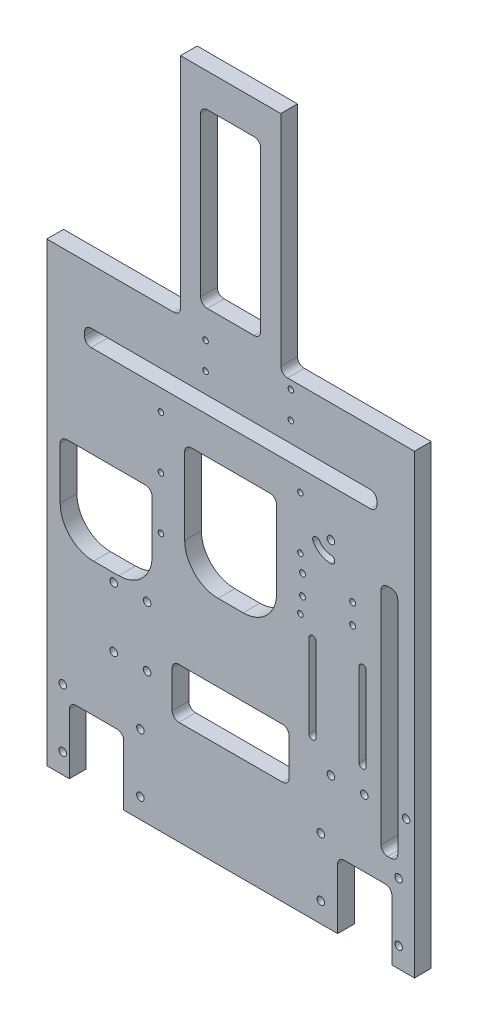
SolidWorks part; units mm, degrees
ref_plane "Front" through (0, 0, 0) normal (0, 0, 1) x (1, 0, 0)
ref_plane "Top" through (0, 0, 0) normal (0, 1, 0) x (1, 0, 0)
ref_plane "Right" through (0, 0, 0) normal (1, 0, 0) x (0, 0, -1)
sketch "Esquisse1" plane through (0, 0, 0) normal (0, 0, 1) x (1, 0, 0)
  line L1 (0, 0) -> (220, 0)
  line L2 (0, 0) -> (0, 285)
  line L3 (0, 285) -> (220, 285)
  line L4 (220, 0) -> (220, 285)
  dimension "D1" = 220
  dimension "D2" = 285
extrude "Boss.-Extru.1" add sketch "Esquisse1" along normal blind 10
sketch "Esquisse2" plane through (0, 0, 0) normal (0, -1, 0) x (1, 0, 0)
  line L0 (0, 5) -> (220, 5) construction
  line L1 (0, 10) -> (0, 0) construction
  line L2 (220, 10) -> (220, 0) construction
  line L3 (110, 5) -> (110, 28.0559) construction
  circle A0 centre (110, 5) radius 2
  circle A1 centre (213, 5) radius 2
  circle A2 centre (7, 5) radius 2
  dimension "D1" = 4
  dimension "D2" = 103
extrude "Enlèv. mat.-Extru.1" cut sketch "Esquisse2" against normal blind 8
sketch "Esquisse3" plane through (0, 0, 10) normal (0, 0, 1) x (1, 0, 0)
  line L0 (110, 0) -> (110, 285) construction
  line L1 (0, 0) -> (220, 0) construction
  line L2 (220, 285) -> (0, 285) construction
  line L3 (82.5, 208) -> (137.5, 208)
  line L4 (137.5, 208) -> (137.5, 138)
  line L5 (137.5, 138) -> (82.5, 138)
  line L6 (82.5, 208) -> (82.5, 138)
  line L8 (8, 175) -> (63, 175)
  line L9 (8, 175) -> (8, 120)
  line L10 (8, 120) -> (63, 120)
  line L11 (63, 175) -> (63, 120)
  line L12 (200, 55) -> (210, 55)
  line L13 (200, 55) -> (200, 195)
  line L14 (200, 195) -> (210, 195)
  line L15 (210, 55) -> (210, 195)
  point P11 (110, 138)
  point P12 (110, 208)
  dimension "D1" = 70
  dimension "D2" = 55
  dimension "D3" = 138
  dimension "D4" = 55
  dimension "D5" = 47
  dimension "D6" = 55
  dimension "D7" = 120
  dimension "D8" = 140
  dimension "D9" = 55
  dimension "D10" = 90
  dimension "D11" = 10
extrude "Enlèv. mat.-Extru.2" cut sketch "Esquisse3" against normal through all both and the other way through all
sketch "Esquisse5" plane through (0, 0, 10) normal (0, 0, 1) x (1, 0, 0)
  line L0 (110, 230) -> (110, 0) construction
  line L1 (22.5, 240) -> (197.5, 240)
  line L2 (22.5, 240) -> (22.5, 230)
  line L3 (22.5, 230) -> (197.5, 230)
  line L4 (197.5, 240) -> (197.5, 230)
  line L5 (0, 0) -> (220, 0) construction
  dimension "D1" = 175
  dimension "D2" = 10
  dimension "D3" = 230
extrude "Enlèv. mat.-Extru.3" cut sketch "Esquisse5" against normal through all both and the other way through all
sketch "Esquisse6" plane through (0, 0, 10) normal (0, 0, 1) x (1, 0, 0)
  line L0 (170, 80) -> (190, 80) construction
  line L1 (0, 0) -> (220, 0) construction
  line L2 (137.5, 138) -> (82.5, 138) construction
  line L3 (215, 80) -> (190, 80) construction
  line L4 (168, 193.9299) -> (168, 170.25) construction
  line L5 (186.4274, 170.25) -> (149.5726, 170.25) construction
  line L6 (0, 285) -> (0, 0) construction
  circle A0 centre (190, 80) radius 2.25
  circle A1 centre (170, 80) radius 2.25
  circle A2 centre (215, 80) radius 2.25
  circle A3 centre (153, 176.25) radius 1.75
  circle A4 centre (183, 176.25) radius 1.75
  circle A5 centre (183, 164.25) radius 1.75
  circle A6 centre (153, 164.25) radius 1.75
  point P8 (110, 138)
  dimension "D1" = 4.5
  dimension "D3" = 80
  dimension "D6" = 30
  dimension "D7" = 12
  dimension "D8" = 3.5
  dimension "D2" = 20
  dimension "D4" = 60
  dimension "D5" = 25
  dimension "D9" = 168
  dimension "D10" = 170.25
extrude "Enlèv. mat.-Extru.4" cut sketch "Esquisse6" against normal through all both and the other way through all
sketch "Esquisse7" plane through (0, 0, 10) normal (0, 0, 1) x (1, 0, 0)
  line L0 (110, 0) -> (110, 285) construction
  line L1 (0, 0) -> (220, 0) construction
  line L2 (220, 285) -> (0, 285) construction
  line L3 (68.285, 186) -> (68.285, 217.4) construction
  line L4 (68.285, 186) -> (110, 186) construction
  line L5 (151.715, 186) -> (151.715, 217.4) construction
  line L6 (95, 268) -> (120.5, 268) construction
  line L7 (120.5, 268) -> (120.5, 260) construction
  line L8 (120.5, 260) -> (137.9818, 260) construction
  line L9 (95, 252) -> (120.5, 252) construction
  line L10 (22.5, 240) -> (197.5, 240) construction
  circle A0 centre (68.285, 217.4) radius 1.65
  circle A1 centre (68.285, 186) radius 1.65
  circle A2 centre (68.285, 154.6) radius 1.65
  circle A3 centre (151.715, 154.6) radius 1.65
  circle A4 centre (151.715, 186) radius 1.65
  circle A5 centre (151.715, 217.4) radius 1.65
  circle A6 centre (95, 268) radius 1.65
  circle A7 centre (146, 268) radius 1.65
  circle A8 centre (146, 252) radius 1.65
  circle A9 centre (95, 252) radius 1.65
  dimension "D1" = 31.4
  dimension "D2" = 3.3
  dimension "D5" = 16
  dimension "D6" = 51
  dimension "D9" = 3.3
  dimension "D7" = 15
  dimension "D3" = 83.43
  dimension "D4" = 186
  dimension "D8" = 20
extrude "Enlèv. mat.-Extru.5" cut sketch "Esquisse7" against normal through all both and the other way through all
sketch "Esquisse8" plane through (0, 0, 10) normal (0, 0, 1) x (1, 0, 0)
  line L0 (110, 0) -> (110, 285) construction
  line L1 (0, 0) -> (220, 0) construction
  line L2 (220, 285) -> (0, 285) construction
  line L3 (174, 0) -> (174, 40)
  line L4 (13.5, 0) -> (46, 0)
  line L5 (13.5, 0) -> (13.5, 40)
  line L6 (13.5, 40) -> (46, 40)
  line L7 (46, 0) -> (46, 40)
  line L8 (206.5, 40) -> (174, 40)
  line L9 (206.5, 0) -> (206.5, 40)
  line L10 (206.5, 0) -> (174, 0)
  dimension "D1" = 128
  dimension "D2" = 32.5
  dimension "D3" = 40
extrude "Enlèv. mat.-Extru.6" cut sketch "Esquisse8" against normal through all both and the other way through all
fillet "Congé1" radius 20 4 edges at (137.5, 138, 5) (82.5, 138, 5) (63, 120, 5) (8, 120, 5)
sketch "Esquisse9" plane through (0, 0, 10) normal (0, 0, 1) x (1, 0, 0)
  line L0 (189, 145) -> (189, 95) construction
  line L1 (191.1, 145) -> (191.1, 95)
  line L2 (186.9, 145) -> (186.9, 95)
  line L3 (189, 120) -> (159, 120) construction
  line L4 (174, 120) -> (174, 121.5076) construction
  line L5 (159, 95) -> (159, 145) construction
  line L6 (156.9, 95) -> (156.9, 145)
  line L7 (161.1, 95) -> (161.1, 145)
  line L9 (210, 55) -> (200, 55) construction
  line L10 (200, 55) -> (200, 195) construction
  arc A0 (191.1, 145) -> (186.9, 145) centre (189, 145) ccw
  arc A1 (186.9, 95) -> (191.1, 95) centre (189, 95) ccw
  arc A2 (156.9, 95) -> (161.1, 95) centre (159, 95) ccw
  arc A3 (161.1, 145) -> (156.9, 145) centre (159, 145) ccw
  point P2 (189, 120)
  point P13 (159, 120)
  dimension "D1" = 4.2
  dimension "D2" = 30
  dimension "D3" = 11
  dimension "D4" = 40
  dimension "D5" = 50
extrude "Enlèv. mat.-Extru.7" cut sketch "Esquisse9" against normal through all both and the other way through all
sketch "Esquisse10" plane through (0, 0, 10) normal (0, 0, 1) x (1, 0, 0)
  line L0 (9.5, 0) -> (9.5, 52.9697) construction
  line L1 (0, 0) -> (13.5, 0) construction
  line L2 (0, 285) -> (0, 0) construction
  line L3 (110, 0) -> (110, 48.9194) construction
  line L4 (46, 0) -> (174, 0) construction
  line L5 (32.75, 0) -> (32.75, 52.9697) construction
  circle A0 centre (9.5, 12) radius 2.25
  circle A1 centre (9.5, 47) radius 2.25
  circle A2 centre (210.5, 47) radius 2.25
  circle A3 centre (210.5, 12) radius 2.25
  circle A4 centre (56, 47) radius 2.25
  circle A5 centre (56, 12) radius 2.25
  circle A6 centre (164, 12) radius 2.25
  circle A7 centre (164, 47) radius 2.25
  dimension "D2" = 4.5
  dimension "D3" = 35
  dimension "D4" = 12
  dimension "D5" = 46.5
  dimension "D1" = 9.5
extrude "Enlèv. mat.-Extru.8" cut sketch "Esquisse10" against normal through all both and the other way through all
sketch "Esquisse11" plane through (0, 0, 10) normal (0, 0, 1) x (1, 0, 0)
  line L0 (110, 62) -> (110, 0) construction
  line L1 (75, 92) -> (145, 92)
  line L2 (75, 92) -> (75, 62)
  line L3 (75, 62) -> (145, 62)
  line L4 (145, 92) -> (145, 62)
  line L5 (46, 0) -> (174, 0) construction
  dimension "D1" = 70
  dimension "D2" = 30
  dimension "D3" = 62
extrude "Enlèv. mat.-Extru.9" cut sketch "Esquisse11" against normal through all both and the other way through all
sketch "Esquisse12" plane through (0, 0, 10) normal (0, 0, 1) x (1, 0, 0)
  line L0 (220, 0) -> (220, 285) construction
  line L1 (46, 0) -> (174, 0) construction
  line L2 (170, 202) -> (161.3397, 197) construction
  line L3 (170, 192) -> (170, 202) construction
  circle A0 centre (170, 202) radius 2.25
  arc A1 (161.3397, 197) -> (170, 192) centre (170, 202) ccw construction
  arc A2 (159.3912, 195.875) -> (170, 189.75) centre (170, 202) ccw
  arc A3 (163.2883, 198.125) -> (170, 194.25) centre (170, 202) ccw
  arc A4 (163.2883, 198.125) -> (159.3912, 195.875) centre (161.3397, 197) ccw
  arc A5 (170, 189.75) -> (170, 194.25) centre (170, 192) ccw
  point P9 (165, 193.3397)
  dimension "D1" = 4.5
  dimension "D2" = 50
  dimension "D3" = 202
  dimension "D4" = 4.5
  dimension "D5" = 10
  dimension "D6" = 60
extrude "Enlèv. mat.-Extru.10" cut sketch "Esquisse12" against normal through all both and the other way through all
sketch "Esquisse13" plane through (0, 0, 10) normal (0, 0, 1) x (1, 0, 0)
  line L0 (50, 123.132) -> (50, 97) construction
  line L1 (50, 97) -> (30.3926, 97) construction
  line L2 (46, 0) -> (174, 0) construction
  line L3 (0, 285) -> (0, 0) construction
  circle A0 centre (40, 115) radius 2.25
  circle A1 centre (60, 115) radius 2.25
  circle A2 centre (60, 79) radius 2.25
  circle A3 centre (40, 79) radius 2.25
  dimension "D1" = 36
  dimension "D2" = 20
  dimension "D3" = 4.5
  dimension "D4" = 97
  dimension "D5" = 40
extrude "Enlèv. mat.-Extru.11" cut sketch "Esquisse13" against normal through all both and the other way through all
sketch "Esquisse14" plane through (0, 0, 10) normal (0, 0, 1) x (1, 0, 0)
  line L0 (110, 0) -> (110, 159.9943) construction
  line L1 (0, 285) -> (80, 285)
  line L2 (0, 285) -> (0, 273)
  line L3 (0, 273) -> (80, 273)
  line L4 (80, 285) -> (80, 273)
  line L5 (46, 0) -> (174, 0) construction
  line L6 (140, 285) -> (140, 273)
  line L7 (220, 273) -> (140, 273)
  line L8 (220, 285) -> (220, 273)
  line L9 (220, 285) -> (140, 285)
  dimension "D1" = 12
  dimension "D2" = 80
extrude "Enlèv. mat.-Extru.12" cut sketch "Esquisse14" against normal through all both and the other way through all
sketch "Esquisse15" plane through (0, 0, 10) normal (0, 0, 1) x (1, 0, 0)
  line L0 (140, 285) -> (80, 285) construction
  line L1 (80, 285) -> (140, 285)
  line L2 (80, 285) -> (80, 408)
  line L3 (80, 408) -> (140, 408)
  line L4 (140, 285) -> (140, 408)
  line L5 (110, 408) -> (110, 0) construction
  line L6 (46, 0) -> (174, 0) construction
  dimension "D1" = 60
  dimension "D2" = 123
extrude "Boss.-Extru.2" add sketch "Esquisse15" against normal up to vertex (10 mm away) up to point (13.5, 0, 0)
sketch "Esquisse16" plane through (0, 0, 10) normal (0, 0, 1) x (1, 0, 0)
  line L0 (110, 388) -> (110, 408) construction
  line L1 (92, 285) -> (128, 285)
  line L2 (92, 285) -> (92, 388)
  line L3 (92, 388) -> (128, 388)
  line L4 (128, 285) -> (128, 388)
  line L5 (140, 408) -> (80, 408) construction
  line L6 (140, 273) -> (140, 408) construction
  line L7 (80, 273) -> (0, 273) construction
  dimension "D1" = 12
  dimension "D2" = 20
  dimension "D3" = 12
extrude "Enlèv. mat.-Extru.13" cut sketch "Esquisse16" against normal through all both and the other way through all
fillet "Congé2" radius 4 26 edges at (137.5, 208, 5) (82.5, 208, 5) (197.5, 230, 5) (197.5, 240, 5) (22.5, 240, 5) (22.5, 230, 5) (63, 175, 5) (8, 175, 5) (200, 195, 5) (210, 195, 5) (210, 55, 5) (200, 55, 5) (206.5, 40, 5) (174, 40, 5) (46, 40, 5) (13.5, 40, 5) (75, 62, 5) (145, 62, 5) (145, 92, 5) (75, 92, 5) (92, 388, 5) (128, 388, 5) (128, 285, 5) (92, 285, 5) (140, 273, 5) (80, 273, 5)
